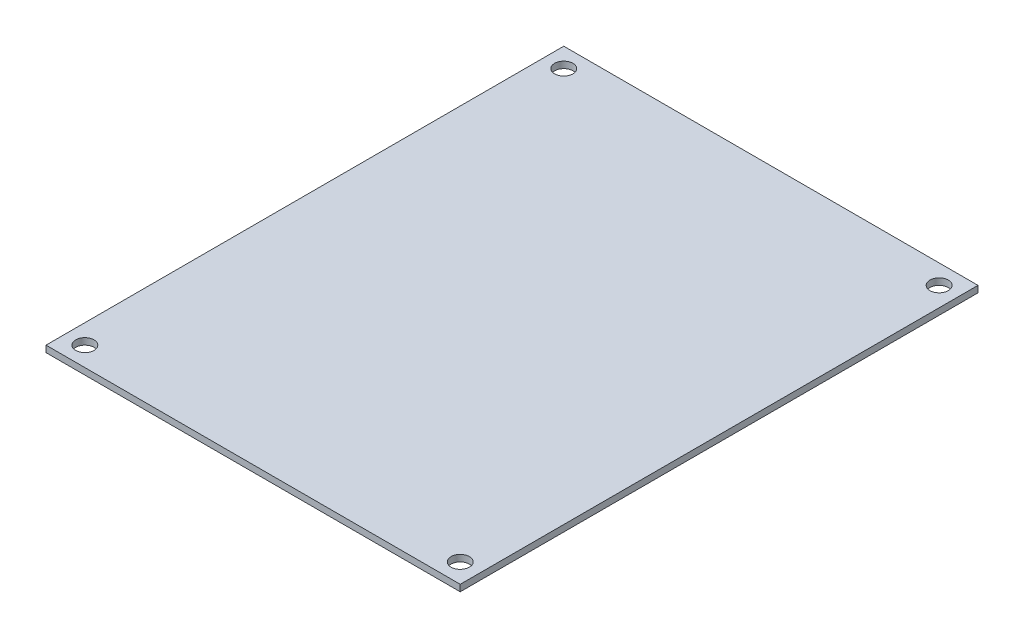
SolidWorks part; units mm, degrees
ref_plane "Front" through (0, 0, 0) normal (0, 0, 1) x (1, 0, 0)
ref_plane "Top" through (0, 0, 0) normal (0, 1, 0) x (1, 0, 0)
ref_plane "Right" through (0, 0, 0) normal (1, 0, 0) x (0, 0, -1)
sketch "Sketch1" plane through (0, 0, 0) normal (0, 1, 0) x (1, 0, 0)
  line L1 (-50.8, -63.5) -> (50.8, -63.5)
  line L2 (-50.8, -63.5) -> (-50.8, 63.5)
  line L3 (-50.8, 63.5) -> (50.8, 63.5)
  line L4 (50.8, -63.5) -> (50.8, 63.5)
  line L5 (-50.8, -63.5) -> (50.8, 63.5) construction
  line L6 (-50.8, 63.5) -> (50.8, -63.5) construction
  point P0 (0, 0)
  dimension "D1" = 127
  dimension "D2" = 101.6
extrude "Boss-Extrude1" add sketch "Sketch1" along normal blind 1.6
hole_wizard "M4 Clearance Hole1" positions "Sketch2" profile "Sketch3" hole size "M4" standard "ANSI Metric"
sketch "Sketch2" plane through (0, 1.6, 0) normal (0, 1, 0) x (1, 0, 0)
  line L1 (-46.0375, 58.7375) -> (46.0375, 58.7375)
  line L2 (-46.0375, 58.7375) -> (-46.0375, -58.7375)
  line L3 (-46.0375, -58.7375) -> (46.0375, -58.7375)
  line L4 (46.0375, 58.7375) -> (46.0375, -58.7375)
  line L5 (-46.0375, 58.7375) -> (46.0375, -58.7375) construction
  line L6 (-46.0375, -58.7375) -> (46.0375, 58.7375) construction
  line L7 (50.8, -63.5) -> (50.8, 63.5) construction
  line L8 (-50.8, -63.5) -> (50.8, -63.5) construction
  point P0 (-46.0375, 58.7375)
  point P2 (46.0375, 58.7375)
  point P4 (46.0375, -58.7375)
  point P6 (-46.0375, -58.7375)
  point P97 (0, 0)
  point P99 (0, 0)
  point P100 (0, 0)
  point P101 (0, 0)
  point P102 (0, 0)
  point P103 (40.3741, -46.0104)
  dimension "D1" = 4.7625
  dimension "D2" = 4.7625
sketch "Sketch3" plane through (-46.0375, 1.6, -58.7375) normal (1, 0, 0) x (0, 0, 1)
  line L0 (0, 0) -> (0, 51.3519)
  line L1 (0, 51.3519) -> (2.25, 50)
  line L2 (2.25, 50) -> (2.25, 0)
  line L5 (2.25, 0) -> (0, 0)
  line L10 (0, 51.3519) -> (-2.25, 50) construction
  line L11 (0, -6.35) -> (0, 107.95) construction
  dimension "Hole Dia." = 4.5
  dimension "Hole Depth" = 50
  dimension "Drill Angle" = 118
